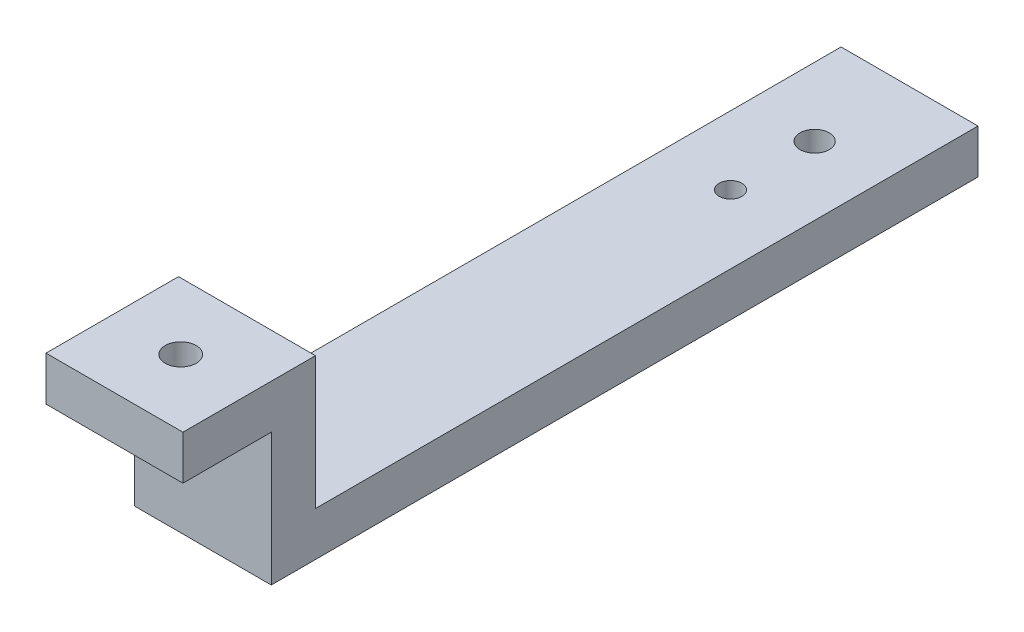
SolidWorks part; units mm, degrees
material "Galvanized Steel"
ref_plane "Front Plane" through (0, 0, 0) normal (0, 0, 1) x (1, 0, 0)
ref_plane "Top Plane" through (0, 0, 0) normal (0, 1, 0) x (1, 0, 0)
ref_plane "Right Plane" through (0, 0, 0) normal (1, 0, 0) x (0, 0, -1)
sketch "Sketch1" plane through (0, 0, 0) normal (1, 0, 0) x (0, 0, -1)
  line L0 (0, 0) -> (30, 0)
  line L1 (30, 0) -> (30, -29.972)
  line L2 (30, -29.972) -> (180, -29.972)
  dimension "D1" = 30
  dimension "D2" = 29.972
extrude "Extrude-Thin1" add sketch "Sketch1" along normal blind 31 thin contours L0 L1 L2 thin type one direction wall 10
sketch "Sketch6" plane through (0, 0, 0) normal (0, 1, 0) x (1, 0, 0)
  line L0 (0, 0) -> (0, 30) construction
  line L2 (31, 30) -> (0, 30) construction
  circle A0 centre (15.5, 15) radius 3.5
  dimension "D1" = 7
  dimension "D2" = 15.5
  dimension "D3" = 15
extrude "Cut-Extrude1" cut sketch "Sketch6" against normal blind 10
sketch "Sketch7" plane through (0, -29.972, 0) normal (0, 1, 0) x (1, 0, 0)
  line L0 (31, 30) -> (0, 30) construction
  line L2 (0, 30) -> (0, 180) construction
  circle A0 centre (15.494, 158.524) radius 3.302
  dimension "D1" = 6.604
  dimension "D3" = 15.494
  dimension "D2" = 128.524
extrude "Cut-Extrude3" cut sketch "Sketch7" against normal blind 10.16
hole_wizard "#97 (0.203) Diameter Hole1" positions "Sketch8" profile "Sketch9" hole size "#97" standard "ANSI Inch"
sketch "Sketch8" plane through (0, -29.972, 0) normal (0, 1, 0) x (1, 0, 0)
  circle A0 centre (15.494, 158.524) radius 3.302 construction
  point P0 (15.494, 139.474)
  point P5 (0, 0)
  dimension "D1" = 19.05
sketch "Sketch9" plane through (15.494, -29.972, -139.474) normal (1, 0, 0) x (0, 0, 1)
  line L0 (0, 0) -> (0, 26.9491)
  line L1 (0, 26.9491) -> (2.5781, 25.4)
  line L2 (2.5781, 25.4) -> (2.5781, 0)
  line L5 (2.5781, 0) -> (0, 0)
  line L10 (0, 26.9491) -> (-2.5781, 25.4) construction
  line L11 (0, -6.35) -> (0, 107.95) construction
  dimension "Hole Dia." = 5.1562
  dimension "Hole Depth" = 25.4
  dimension "Drill Angle" = 118
